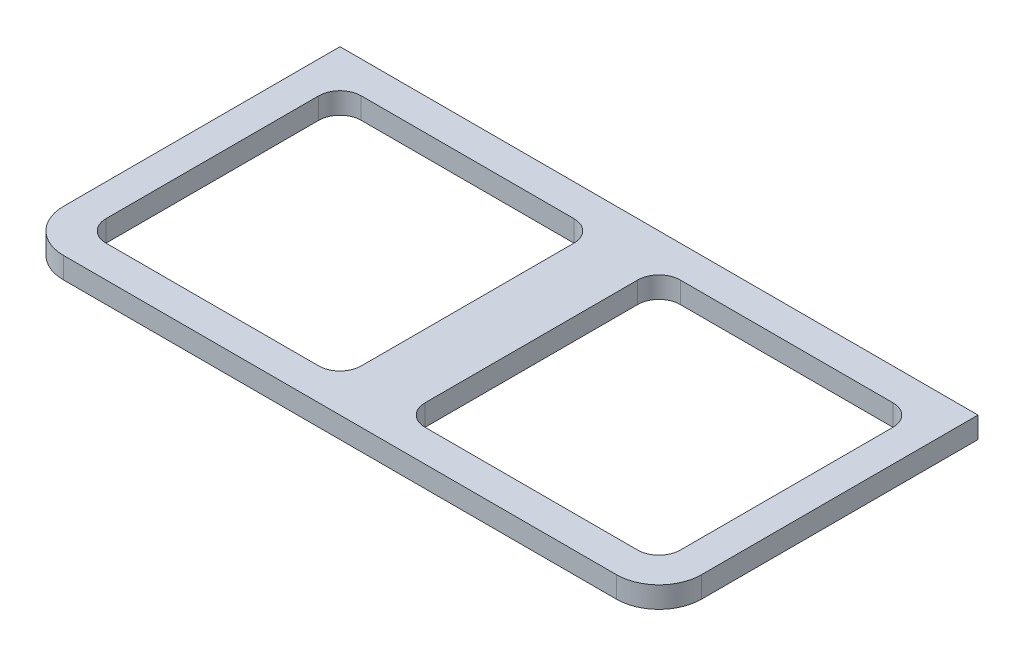
SolidWorks part; units mm, degrees
ref_plane "Ebene vorne" through (0, 0, 0) normal (0, 0, 1) x (1, 0, 0)
ref_plane "Ebene oben" through (0, 0, 0) normal (0, 1, 0) x (1, 0, 0)
ref_plane "Ebene rechts" through (0, 0, 0) normal (1, 0, 0) x (0, 0, -1)
sketch "Skizze1" plane through (0, 10, 0) normal (0, 1, 0) x (1, 0, 0)
  line L0 (-130, -75) -> (130, -75) construction
  line L1 (0, -75) -> (130, -75)
  line L2 (0, -75) -> (0, 75)
  line L3 (0, 75) -> (150, 75)
  line L4 (150, -55) -> (150, 75)
  line L5 (150, -55) -> (150, 75) construction
  line L6 (15, -60) -> (15, -75) construction
  line L7 (15, 60) -> (135, 60)
  line L8 (15, 60) -> (15, -60)
  line L9 (15, -60) -> (135, -60)
  line L10 (135, 60) -> (135, -60)
  line L11 (15, -75) -> (15, -60) construction
  line L12 (0, -60) -> (15, -60) construction
  line L13 (135, 60) -> (135, 75) construction
  line L14 (135, 60) -> (150, 60) construction
  arc A0 (130, -75) -> (150, -55) centre (130, -55) ccw
  arc A1 (130, -75) -> (150, -55) centre (130, -55) ccw construction
  dimension "D1" = 120
extrude "Linear austragen1" add sketch "Skizze1" along normal blind 10
fillet "Verrundung2" radius 10 4 edges at (15, 15, 60) (135, 15, 60) (135, 15, -60) (15, 15, -60)
mirror "Spiegeln1" about plane through (0, 20, 75) normal (1, 0, 0) of "Verrundung2", "Linear austragen1"
